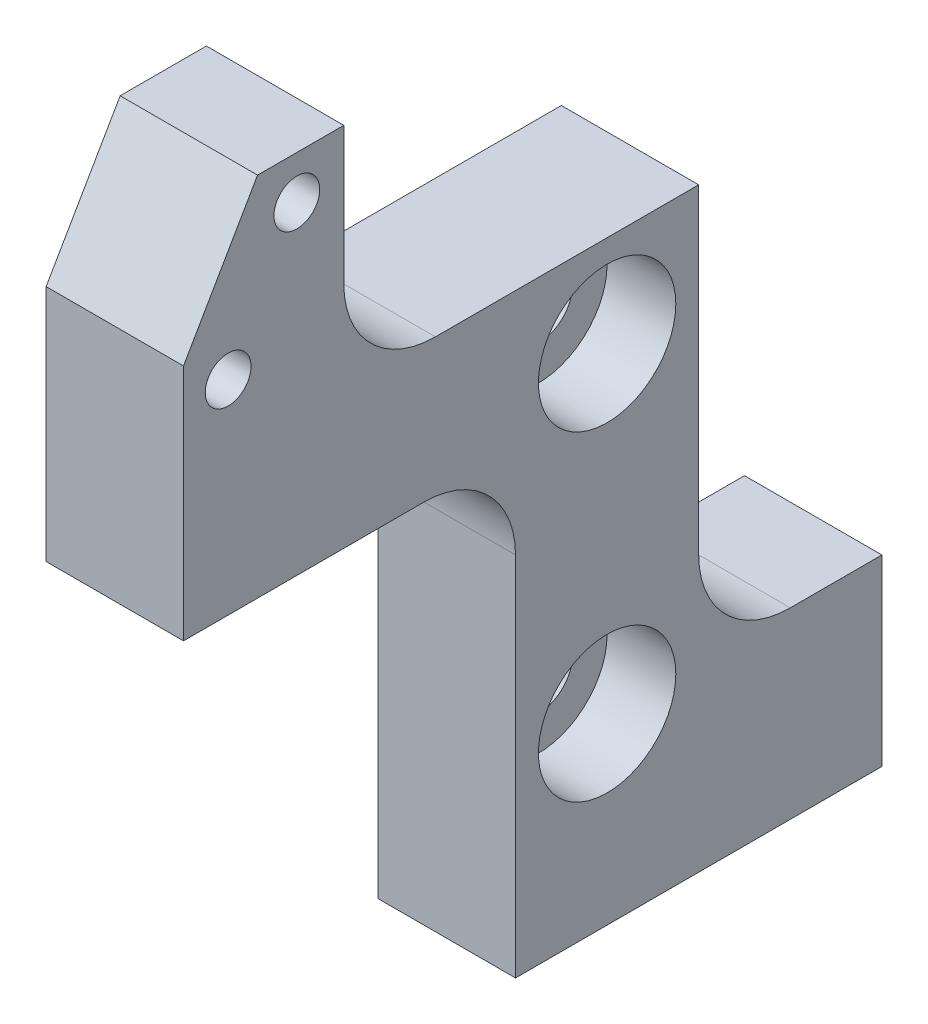
SolidWorks part; units mm, degrees
ref_plane "Front Plane" through (0, 0, 0) normal (0, 0, 1) x (1, 0, 0)
ref_plane "Top Plane" through (0, 0, 0) normal (0, 1, 0) x (1, 0, 0)
ref_plane "Right Plane" through (0, 0, 0) normal (1, 0, 0) x (0, 0, -1)
sketch "Sketch1" plane through (0, 0, 0) normal (1, 0, 0) x (0, 0, -1)
  line L0 (30.5, 0) -> (14.5, 0)
  line L1 (14.5, 0) -> (14.5, 20)
  line L2 (14.5, 20) -> (0, 20)
  line L3 (0, 20) -> (0, 30.4)
  line L4 (0, 30.4) -> (3.2332, 36)
  line L5 (3.2332, 36) -> (7, 36)
  line L6 (7, 36) -> (7, 26)
  line L7 (7, 26) -> (22.5, 26)
  line L8 (22.5, 26) -> (22.5, 8)
  line L9 (22.5, 8) -> (30.5, 8)
  line L10 (30.5, 8) -> (30.5, 0)
  line L11 (1.95, 28.91) -> (4.95, 34.1062) construction
  circle A0 centre (18.5, 8) radius 1.5
  circle A1 centre (18.5, 22) radius 1.5
  circle A2 centre (1.95, 28.91) radius 1
  circle A3 centre (4.95, 34.1062) radius 1
  dimension "D3" = 3
  dimension "D4" = 2
  dimension "D1" = 8
  dimension "D2" = 14.5
  dimension "D5" = 16
  dimension "D6" = 12
  dimension "D7" = 14
  dimension "D8" = 8
  dimension "D9" = 20
  dimension "D10" = 120
  dimension "D11" = 5.6
  dimension "D12" = 6
  dimension "D13" = 1.95
  dimension "D14" = 7.09
  dimension "D15" = 7
  dimension "D16" = 10
  dimension "D17" = 36
extrude "Boss-Extrude1" add sketch "Sketch1" along normal blind 6
fillet "Fillet1" radius 4 3 edges at (3, 8, -22.5) (3, 20, -14.5) (3, 26, -7)
hole_wizard "Tap Drill for M3x0.5 Tap1" positions "Sketch3" profile "Sketch2" hole size "M3x0.5" standard "ANSI Metric"
sketch "Sketch3" plane through (0, 0, 0) normal (0, -1, 0) x (-1, 0, 0)
  line L0 (-6, 14.5) -> (-6, 30.5) construction
  line L1 (-6, 30.5) -> (0, 30.5) construction
  point P0 (-3, 17.5)
  point P2 (-3, 27.5)
  dimension "D1" = 3
  dimension "D2" = 3
  dimension "D3" = 10
sketch "Sketch2" plane through (3, 0, -17.5) normal (1, 0, 0) x (0, 0, -1)
  line L0 (0, 0) -> (0, 4)
  line L1 (0, 4) -> (1.25, 4)
  line L2 (1.25, 4) -> (1.25, 0)
  line L5 (1.25, 0) -> (0, 0)
  line L10 (0, 4) -> (-1.25, 4) construction
  line L11 (0, -6.35) -> (0, 107.95) construction
  dimension "Hole Dia." = 2.5
  dimension "Hole Depth" = 4
  dimension "Drill Angle" = 180
sketch "Sketch4" plane through (0, 0, 0) normal (0, -1, 0) x (1, 0, 0)
  line L0 (6, -30.5) -> (0, -30.5) construction
  line L1 (0, -14.5) -> (0, -30.5) construction
  circle A0 centre (3, -22.5) radius 1
  dimension "D1" = 2
  dimension "D2" = 8
  dimension "D3" = 3
extrude "Cut-Extrude1" cut sketch "Sketch4" against normal blind 3
sketch "Sketch5" plane through (6, 0, 0) normal (1, 0, 0) x (0, 0, -1)
  circle A0 centre (18.5, 22) radius 3
  circle A1 centre (18.5, 8) radius 3
  dimension "D1" = 6
extrude "Cut-Extrude2" cut sketch "Sketch5" against normal blind 3
